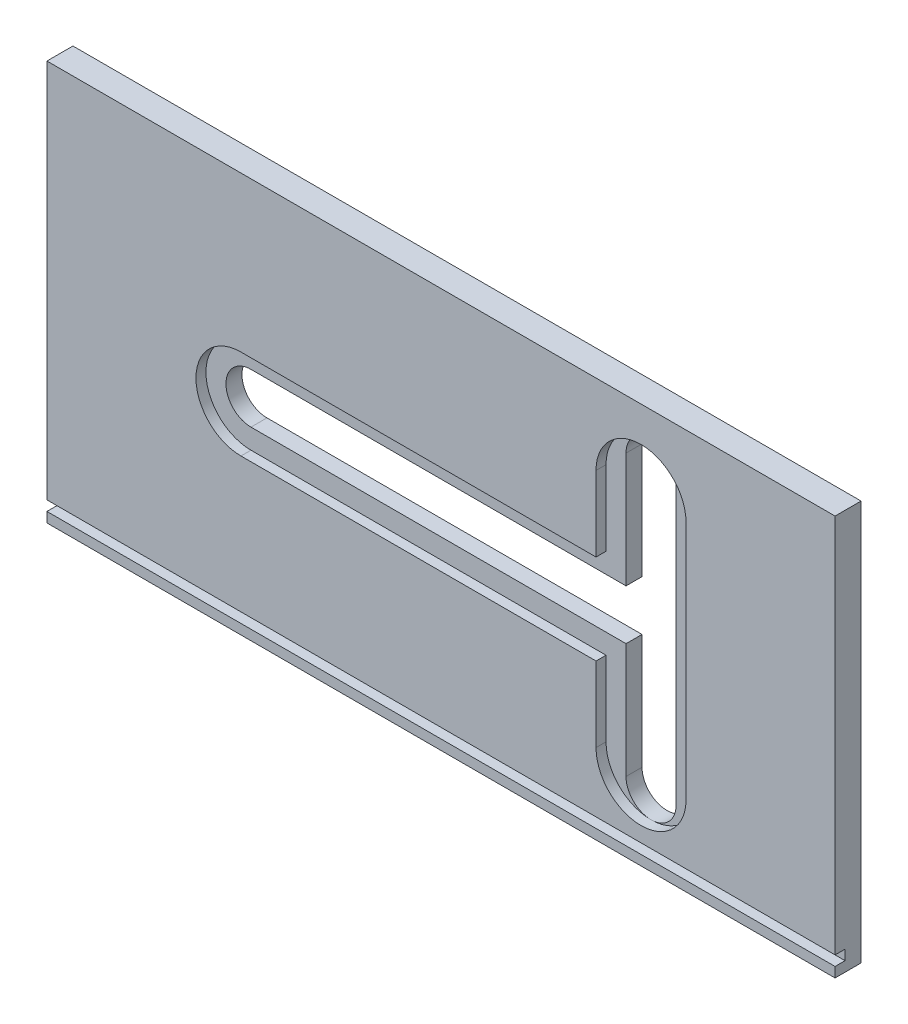
SolidWorks part; units mm, degrees
ref_plane "正面" through (0, 0, 0) normal (0, 0, 1) x (1, 0, 0)
ref_plane "平面" through (0, 0, 0) normal (0, 1, 0) x (1, 0, 0)
ref_plane "右側面" through (0, 0, 0) normal (1, 0, 0) x (0, 0, -1)
sketch "ｽｹｯﾁ1" plane through (0, 0, 0) normal (0, 0, 1) x (1, 0, 0)
  line L1 (-69.2801, 161.5071) -> (324.7199, 161.5071)
  line L2 (-69.2801, 161.5071) -> (-69.2801, -38.4929)
  line L3 (-69.2801, -38.4929) -> (324.7199, -38.4929)
  line L4 (324.7199, 161.5071) -> (324.7199, -38.4929)
  dimension "D1" = 394
  dimension "D3" = 200
extrude "ﾎﾞｽ - 押し出し1" add sketch "ｽｹｯﾁ1" along normal blind 13
sketch "ｽｹｯﾁ2" plane through (0, 0, 13) normal (0, 0, 1) x (1, 0, 0)
  line L0 (324.7199, -38.4929) -> (324.7199, 161.5071) construction
  line L1 (324.7199, -33.4929) -> (-69.2801, -33.4929)
  line L2 (324.7199, -33.4929) -> (324.7199, -28.4929)
  line L3 (324.7199, -28.4929) -> (-69.2801, -28.4929)
  line L4 (-69.2801, -33.4929) -> (-69.2801, -28.4929)
  line L5 (-69.2801, 161.5071) -> (-69.2801, -38.4929) construction
  line L7 (-69.2801, -38.4929) -> (324.7199, -38.4929) construction
  dimension "D1" = 5
  dimension "D2" = 394
  dimension "D3" = 5
extrude "ｶｯﾄ - 押し出し1" cut sketch "ｽｹｯﾁ2" against normal blind 5
sketch "ｽｹｯﾁ3" plane through (0, 0, 13) normal (0, 0, 1) x (1, 0, 0)
  line L0 (27.7199, 61.5071) -> (-69.2801, 61.5071) construction
  line L1 (27.7199, 74.0071) -> (215.2199, 74.0071)
  line L2 (-69.2801, 161.5071) -> (-69.2801, -28.4929) construction
  line L3 (27.7199, 49.0071) -> (215.2199, 49.0071)
  line L4 (215.2199, 131.5071) -> (215.2199, 74.0071)
  line L6 (227.7199, -8.4929) -> (324.7199, -8.4929) construction
  line L8 (96.6525, 74.0071) -> (96.6525, 161.5071) construction
  line L9 (324.7199, 161.5071) -> (-69.2801, 161.5071) construction
  line L10 (111.609, 49.0071) -> (111.609, -38.4929) construction
  line L11 (-69.2801, -38.4929) -> (324.7199, -38.4929) construction
  line L12 (215.2199, 49.0071) -> (215.2199, -8.4929)
  line L13 (324.7199, -28.4929) -> (324.7199, 161.5071) construction
  line L16 (240.2199, 131.5071) -> (240.2199, -8.4929)
  arc A0 (215.2199, 131.5071) -> (240.2199, 131.5071) centre (227.7199, 131.5071) cw
  arc A1 (27.7199, 49.0071) -> (27.7199, 74.0071) centre (27.7199, 61.5071) cw
  arc A2 (215.2199, -8.4929) -> (240.2199, -8.4929) centre (227.7199, -8.4929) ccw
  dimension "D1" = 200
  dimension "D3" = 25
  dimension "D5" = 25
extrude "ｶｯﾄ - 押し出し2" cut sketch "ｽｹｯﾁ3" against normal through all
sketch "ｽｹｯﾁ6" plane through (0, 0, 13) normal (0, 0, 1) x (1, 0, 0)
  line L0 (324.7199, 161.5071) -> (-69.2801, 161.5071) construction
  line L1 (27.7199, 84.0071) -> (205.2199, 84.0071)
  line L2 (27.7199, 39.0071) -> (205.2199, 39.0071)
  line L3 (205.2199, 121.5071) -> (205.2199, 84.0071)
  line L4 (-69.2801, -38.4929) -> (324.7199, -38.4929) construction
  line L5 (95.8401, 84.0071) -> (95.8401, 161.5071) construction
  line L6 (110.7965, 39.0071) -> (110.7965, -38.4929) construction
  line L7 (205.2199, 39.0071) -> (205.2199, 1.5071)
  line L8 (250.2199, 121.5071) -> (250.2199, 1.5071)
  line L9 (27.7199, 61.5071) -> (-69.2801, 61.5071) construction
  line L10 (-69.2801, 161.5071) -> (-69.2801, -28.4929) construction
  line L11 (227.7199, -13.6641) -> (324.7199, -13.6641) construction
  line L12 (324.7199, -28.4929) -> (324.7199, 161.5071) construction
  line L15 (215.2199, 49.0071) -> (215.2199, -8.4929) construction
  arc A0 (27.7199, 84.0071) -> (27.7199, 39.0071) centre (27.7199, 61.5071) ccw
  arc A1 (27.7199, 74.0071) -> (27.7199, 49.0071) centre (27.7199, 61.5071) ccw construction
  arc A2 (205.2199, 121.5071) -> (250.2199, 121.5071) centre (227.7199, 121.5071) cw
  arc A3 (205.2199, 1.5071) -> (250.2199, 1.5071) centre (227.7199, 1.5071) ccw
  arc A4 (240.2199, 131.5071) -> (215.2199, 131.5071) centre (227.7199, 131.5071) ccw construction
  dimension "D4" = 10
  dimension "D6" = 0
  dimension "D7" = 10
  dimension "D1" = 45
  dimension "D2" = 45
  dimension "D3" = 200
extrude "ｶｯﾄ - 押し出し3" cut sketch "ｽｹｯﾁ6" against normal blind 5
